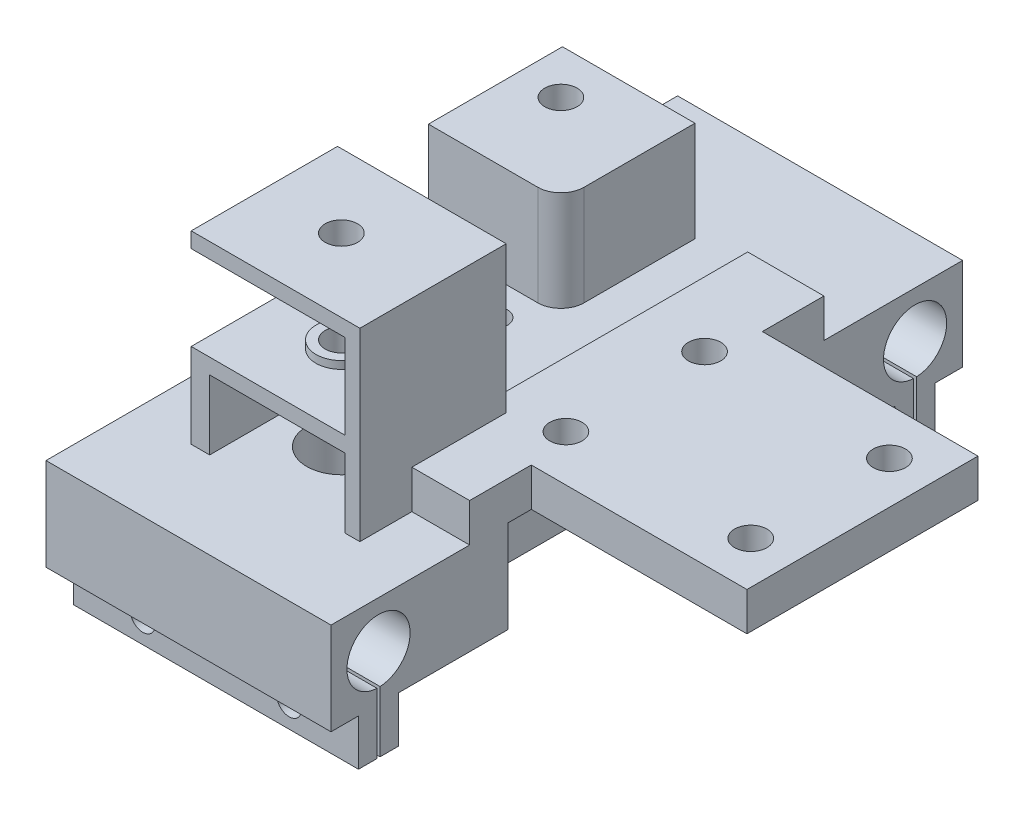
SolidWorks part; units mm, degrees
ref_plane "Спереди" through (0, 0, 0) normal (0, 0, 1) x (1, 0, 0)
ref_plane "Сверху" through (0, 0, 0) normal (0, 1, 0) x (1, 0, 0)
ref_plane "Справа" through (0, 0, 0) normal (1, 0, 0) x (0, 0, -1)
other "Configuration Table"
sketch "Sketch1" plane through (0, 0, 0) normal (0, 1, 0) x (1, 0, 0)
  line L0 (0, 0) -> (12, 0) construction
  line L1 (-17.5, -15) -> (17.5, -15)
  line L2 (-17.5, -15) -> (-17.5, 15)
  line L3 (-17.5, 15) -> (17.5, 15)
  line L4 (17.5, -15) -> (17.5, 15)
  line L5 (-17.5, -15) -> (17.5, 15) construction
  line L6 (-17.5, 15) -> (17.5, -15) construction
  line L7 (12, 0) -> (12, 9) construction
  line L8 (0, 0) -> (0, 10.8794) construction
  line L9 (-12, -9) -> (-12, -15) construction
  line L10 (-12, 9) -> (-12, 15) construction
  line L11 (-12, 9) -> (-17.5, 9) construction
  line L12 (12, 9) -> (17.5, 9) construction
  circle A0 centre (12, 9) radius 2.1
  circle A1 centre (12, -9) radius 2.1
  circle A2 centre (-12, -9) radius 2.1
  circle A3 centre (-12, 9) radius 2.1
  point P0 (0, 0)
  dimension "D3" = 4.2
  dimension "D1" = 35
  dimension "D2" = 30
  dimension "D4" = 18
  dimension "D5" = 24
extrude "Boss-Extrude1" add sketch "Sketch1" along normal blind 5
sketch "Sketch2" plane through (-17.5, 0, 0) normal (-1, 0, 0) x (0, 0, 1)
  line L1 (-15, 5) -> (15, 5)
  line L2 (-15, 5) -> (-15, -12)
  line L3 (-15, -12) -> (15, -12)
  line L4 (15, 5) -> (15, -12)
  dimension "D1" = 17
extrude "Boss-Extrude2" add sketch "Sketch2" along normal blind 5
sketch "Sketch3" plane through (17.5, 0, 0) normal (1, 0, 0) x (0, 0, -1)
  line L0 (15, -12) -> (-15, -12) construction
  line L1 (-41, 0) -> (41, 0)
  line L2 (0, 0) -> (0, -12)
  line L3 (-32.23, -12) -> (32.23, -12)
  line L4 (41, 0) -> (41, -12)
  line L5 (-34.83, -6) -> (34.83, -6) construction
  line L6 (34.83, -6) -> (34.83, -17.5071) construction
  line L7 (34.63, -18) -> (32.23, -18)
  line L9 (35.03, -12) -> (35.03, -18)
  line L10 (35.03, -18) -> (37.43, -18)
  line L11 (37.43, -12) -> (37.43, -18)
  line L12 (32.23, -12) -> (32.23, -18)
  line L14 (34.63, -12) -> (34.63, -18)
  line L15 (34.63, -12) -> (34.63, -10.0951)
  line L16 (35.03, -10.0951) -> (35.03, -12)
  line L18 (37.43, -12) -> (41, -12)
  line L19 (-34.83, -6) -> (-34.83, -17.5071) construction
  line L20 (-37.43, -12) -> (-41, -12)
  line L21 (-35.03, -10.0951) -> (-35.03, -12)
  line L22 (-34.63, -12) -> (-34.63, -10.0951)
  line L23 (-34.63, -12) -> (-34.63, -18)
  line L24 (-32.23, -12) -> (-32.23, -18)
  line L25 (-37.43, -12) -> (-37.43, -18)
  line L26 (-35.03, -18) -> (-37.43, -18)
  line L27 (-35.03, -12) -> (-35.03, -18)
  line L28 (-34.63, -18) -> (-32.23, -18)
  line L29 (-41, 0) -> (-41, -12)
  arc A0 (35.03, -10.0951) -> (34.63, -10.0951) centre (34.83, -6) ccw
  arc A1 (-35.03, -10.0951) -> (-34.63, -10.0951) centre (-34.83, -6) cw
  point P22 (0, -6)
  dimension "D2" = 8.2
  dimension "D1" = 41
  dimension "D3" = 6
  dimension "D4" = 0.2
  dimension "D5" = 2.4
  dimension "D6" = 69.66
extrude "Boss-Extrude3" add sketch "Sketch3" against normal blind 37 from offset 28 contours A1 L22 L23 L28 L24 L3 L12 L7 L14 L15 A0 L16 L9 L10 L11 L18 L4 L1 L29 L20 L25 L26 L27 L21 offset against normal yes
sketch "Sketch5" plane through (-22.5, 0, 0) normal (-1, 0, 0) x (0, 0, 1)
  line L0 (0, 0) -> (0, -11.9864) construction
  line L1 (15, 0) -> (15, 5) construction
  line L2 (-18, -12) -> (18, -12)
  line L3 (-18, -12) -> (-18, 0.0136)
  line L4 (-18, 0.0136) -> (18, 0.0136)
  line L5 (18, -12) -> (18, 0.0136)
  line L6 (-18, -12) -> (18, 0.0136) construction
  line L7 (-18, 0.0136) -> (18, -12) construction
  line L8 (32.23, -12) -> (-32.23, -12) construction
  point P2 (0, -5.9932)
  dimension "D1" = 3
extrude "Cut-Extrude1" cut sketch "Sketch5" against normal up to next from offset 4.5 offset against normal yes
sketch "Sketch6" plane through (0, 5, 0) normal (0, 1, 0) x (1, 0, 0)
  line L0 (-22.5, 0) -> (-22.5, -20.25) construction
  line L1 (-22.5, 15) -> (-22.5, -15) construction
  line L2 (-22.5, -20.25) -> (-29.9, -20.25) construction
  line L3 (-22.5, 0) -> (-22.5, 20.25) construction
  line L4 (-22.5, 20.25) -> (-41.9, 20.25) construction
  line L5 (-29.9, -20.25) -> (-20.4, -20.25) construction
  line L7 (-20.4, -20.25) -> (-22.5, -20.25)
  line L8 (-20.4, -20.25) -> (-20.4, 15)
  line L9 (-20.4, 15) -> (-22.5, 15)
  line L10 (-22.5, -20.25) -> (-22.5, 15)
  dimension "D3" = 9.5
  dimension "D1" = 20.25
  dimension "D2" = 7.4
  dimension "D4" = 19.4
extrude "Cut-Extrude2" cut sketch "Sketch6" against normal up to surface (5 mm away) up to face at (-21.1667, 0, 0)
sketch "Sketch7" plane through (0, 5, 0) normal (0, 1, 0) x (1, 0, 0)
  line L0 (-20.4, 0) -> (-20.4, -20.25) construction
  line L2 (-20.4, -20.25) -> (-29.9, -20.25) construction
  line L3 (-20.4, 0) -> (-20.4, 20.25) construction
  line L4 (-20.4, 20.25) -> (-41.9, 20.25) construction
  line L6 (-20.4, -15) -> (-20.4, 15) construction
  circle A0 centre (-29.9, -20.25) radius 2.1
  circle A1 centre (-41.9, 20.25) radius 2.1
  point P10 (-20.4, 0)
  dimension "D4" = 4.2
  dimension "D1" = 20.25
  dimension "D2" = 9.5
  dimension "D3" = 21.5
extrude "Cut-Extrude3" cut sketch "Sketch7" against normal up to surface (17 mm away) contours A0 | A1 up to face at (-21.625, -12, 0)
sketch "Sketch8" plane through (0, 0, 0) normal (0, 1, 0) x (1, 0, 0)
  line L0 (-41.9, 20.25) -> (-41.9, 10.25) construction
  line L1 (-47.5, 10.25) -> (-34.9, 10.25)
  line L2 (-47.5, -41) -> (-47.5, 41) construction
  line L3 (-31.9, 13.25) -> (-31.9, 26.0516)
  line L4 (-31.9, 26.0516) -> (-30.3, 26.0516)
  line L5 (-30.3, 26.0516) -> (-30.3, 11.65)
  line L6 (-33.3, 8.65) -> (-47.5, 8.65)
  line L7 (-47.5, 8.65) -> (-47.5, 10.25)
  line L8 (-18, -29.75) -> (-18, -10.75)
  line L9 (-18, -10.75) -> (-19.9, -10.75)
  line L10 (-19.9, -10.75) -> (-19.9, -29.75)
  line L11 (-19.9, -29.75) -> (-18, -29.75)
  line L12 (-18, -18) -> (-18, -15) construction
  line L13 (-29.9, -20.25) -> (-29.9, -10.75) construction
  line L14 (-29.9, -20.25) -> (-29.9, -29.75) construction
  line L15 (-29.9, -29.75) -> (-19.9, -29.75) construction
  line L16 (-29.9, -10.75) -> (-19.9, -10.75) construction
  line L18 (-37.5, -29.75) -> (-39.9, -29.75)
  line L19 (-37.5, -29.75) -> (-37.5, -10.75)
  line L20 (-37.5, -10.75) -> (-39.9, -10.75)
  line L21 (-39.9, -29.75) -> (-39.9, -10.75)
  arc A2 (-30.3, 11.65) -> (-33.3, 8.65) centre (-33.3, 11.65) cw
  arc A3 (-34.9, 10.25) -> (-31.9, 13.25) centre (-34.9, 13.25) ccw
  dimension "D1" = 19
  dimension "D5" = 3
  dimension "D2" = 10
  dimension "D3" = 10
  dimension "D4" = 1.6
  dimension "D6" = 7.6
  dimension "D7" = 10
extrude "Boss-Extrude4" add sketch "Sketch8" along normal blind 11
sketch "Sketch9" plane through (0, 0, 0) normal (0, 1, 0) x (1, 0, 0)
  line L0 (-10.5, 18) -> (-10.5, 41) construction
  line L1 (-10.5, 23) -> (-20.4, 23)
  line L2 (-10.5, 23) -> (-10.5, 15)
  line L3 (-10.5, 15) -> (-20.4, 15)
  line L4 (-20.4, 23) -> (-20.4, 15)
  line L5 (-10.5, -41) -> (-10.5, -18) construction
  line L6 (-10.5, -23) -> (-18, -23)
  line L7 (-10.5, -23) -> (-10.5, -15)
  line L8 (-10.5, -15) -> (-18, -15)
  line L9 (-18, -23) -> (-18, -15)
  dimension "D1" = 8
  dimension "D2" = 8
extrude "Boss-Extrude5" add sketch "Sketch9" along normal up to surface (5 mm away) up to face at (-12, 5, -11.1)
sketch "Sketch10" plane through (0, 11, 0) normal (0, 1, 0) x (1, 0, 0)
  line L0 (-47.5, 8.65) -> (-33.3, 8.65) construction
  line L1 (-30.3, 26.0516) -> (-47.5, 26.0516)
  line L2 (-30.3, 26.0516) -> (-30.3, 11.65)
  line L3 (-33.3, 8.65) -> (-47.5, 8.65)
  line L4 (-47.5, 26.0516) -> (-47.5, 8.65)
  line L5 (-47.5, 8.65) -> (-33.3, 8.65) construction
  arc A0 (-30.3, 11.65) -> (-33.3, 8.65) centre (-33.3, 11.65) cw
  dimension "D1" = 3
extrude "Boss-Extrude6" add sketch "Sketch10" along normal blind 2
sketch "Sketch12" plane through (0, -12, 0) normal (0, -1, 0) x (1, 0, 0)
  circle A0 centre (-41.9, -20.25) radius 2.1
  circle A1 centre (-41.9, -20.25) radius 3.3
  dimension "D1" = 1.2
extrude "Boss-Extrude7" add sketch "Sketch12" against normal blind 1 from surface starting at face at (-41.9, 0, -22.35)
extrude "Boss-Extrude8" add sketch "Sketch12<2>" along normal blind 1 from surface starting at face at (-38.6157, 11, -17.0464)
sketch "Sketch12<2>" plane through (0, -12, 0) normal (0, -1, 0) x (1, 0, 0) same geometry as "Sketch12"
sketch "Sketch13" plane through (0, 11, 0) normal (0, 1, 0) x (1, 0, 0)
  line L1 (-18, -10.75) -> (-39.9, -10.75)
  line L2 (-18, -10.75) -> (-18, -29.75)
  line L3 (-18, -29.75) -> (-39.9, -29.75)
  line L4 (-39.9, -10.75) -> (-39.9, -29.75)
extrude "Boss-Extrude9" add sketch "Sketch13" against normal blind 2
sketch "Sketch14" plane through (0, 11, 0) normal (0, 1, 0) x (1, 0, 0)
  line L6 (-18, -10.75) -> (-19.9, -10.75) construction
  line L7 (-18, -29.75) -> (-19.9, -29.75)
  line L8 (-18, -29.75) -> (-18, -10.75)
  line L9 (-18, -10.75) -> (-19.9, -10.75)
  line L10 (-19.9, -29.75) -> (-19.9, -10.75)
  dimension "D1" = 1.9
extrude "Boss-Extrude10" add sketch "Sketch14" along normal blind 11
sketch "Sketch15" plane through (0, 22, 0) normal (0, 1, 0) x (1, 0, 0)
  line L1 (-18, -29.75) -> (-39.9, -29.75)
  line L2 (-18, -29.75) -> (-18, -10.75)
  line L3 (-18, -10.75) -> (-39.9, -10.75)
  line L4 (-39.9, -29.75) -> (-39.9, -10.75)
extrude "Boss-Extrude11" add sketch "Sketch15" along normal blind 2
sketch "Sketch16" plane through (0, -12, 0) normal (0, -1, 0) x (1, 0, 0)
  circle A0 centre (-29.9, 20.25) radius 2.1
  circle A1 centre (-41.9, -20.25) radius 2.1
extrude "Cut-Extrude4" cut sketch "Sketch16" against normal up to surface (36 mm away) up to face at (-28.95, 24, 20.25)
sketch "Sketch17" plane through (0, 24, 0) normal (0, 1, 0) x (1, 0, 0)
  circle A0 centre (-29.9, -20.25) radius 2.1
  circle A1 centre (-29.9, -20.25) radius 3.3
  dimension "D1" = 1.2
extrude "Boss-Extrude12" add sketch "Sketch17" against normal blind 1 from surface starting at face at (-29.9, 22, 22.35)
extrude "Boss-Extrude13" add sketch "Sketch17<2>" along normal blind 1 from surface starting at face at (-29.9, 11, 22.35)
sketch "Sketch17<2>" plane through (0, 24, 0) normal (0, 1, 0) x (1, 0, 0) same geometry as "Sketch17"
sketch "Sketch19" plane through (0, -12, 0) normal (0, -1, 0) x (1, 0, 0)
  circle A0 centre (-29.9, 20.25) radius 4.5
  dimension "D1" = 9
extrude "Cut-Extrude5" cut sketch "Sketch19" against normal up to next
sketch "Sketch20" plane through (0, 0, 0) normal (0, 1, 0) x (1, 0, 0)
  line L0 (-47.5, 4.15) -> (-34.5, 4.15) construction
  line L1 (-47.5, -41) -> (-47.5, 8.65) construction
  line L2 (-47.5, 4.15) -> (-47.5, -17.85) construction
  line L3 (-44.5, -17.85) -> (-47.5, -17.85) construction
  line L4 (-47.5, 8.65) -> (-33.3, 8.65) construction
  circle A0 centre (-34.5, 4.15) radius 1.75
  circle A1 centre (-44.5, -17.85) radius 1.75
  dimension "D3" = 3.5
  dimension "D1" = 3
  dimension "D2" = 10
  dimension "D4" = 22
  dimension "D5" = 4.5
extrude "Cut-Extrude6" cut sketch "Sketch20" against normal up to next
sketch "Sketch21" plane through (0, 0, -37.43) normal (0, 0, -1) x (-1, 0, 0)
  line L0 (10.5, -15) -> (47.5, -15) construction
  line L1 (10.5, -12) -> (10.5, -18) construction
  line L2 (47.5, -12) -> (47.5, -18) construction
  line L3 (29, -15) -> (29, -12) construction
  line L4 (47.5, -12) -> (10.5, -12) construction
  circle A0 centre (19.5, -15) radius 1.6
  circle A1 centre (38.5, -15) radius 1.6
  dimension "D2" = 3.2
  dimension "D1" = 9
extrude "Cut-Extrude7" cut sketch "Sketch21" against normal through all
